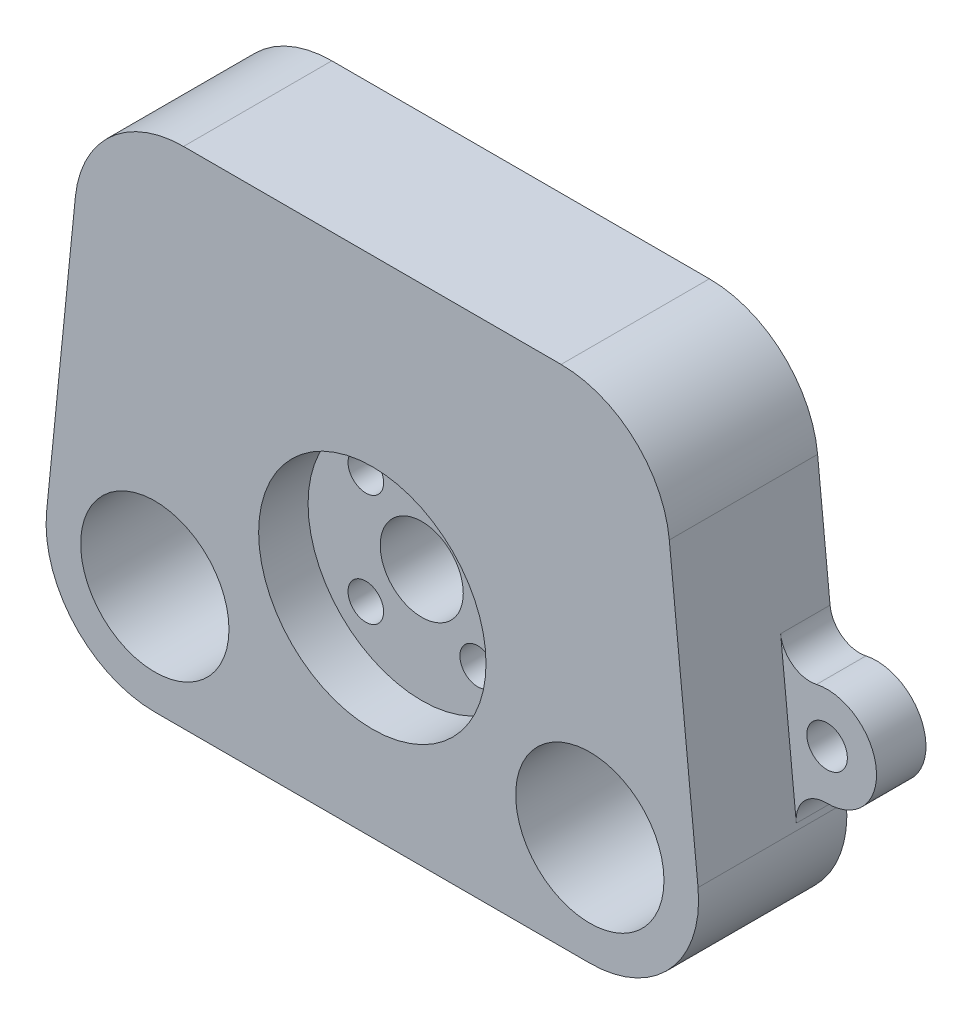
SolidWorks part; units mm, degrees
ref_plane "Front Plane" through (0, 0, 0) normal (0, 0, 1) x (1, 0, 0)
ref_plane "Top Plane" through (0, 0, 0) normal (0, 1, 0) x (1, 0, 0)
ref_plane "Right Plane" through (0, 0, 0) normal (1, 0, 0) x (0, 0, -1)
sketch "PosicionAgujeros" plane through (0, 0, 0) normal (0, 0, 1) x (1, 0, 0)
  line L0 (-18.25, 0) -> (18.25, 0) construction
  line L3 (22, -10) -> (-22, -10) construction
  line L7 (0, 0) -> (0, 20) construction
  line L8 (-20, 20) -> (20, 20) construction
  line L9 (0, 0) -> (5.6569, 5.6569) construction
  circle A1 centre (22, -10) radius 4 construction
  circle A2 centre (18.25, 0) radius 2.5 construction
  circle A3 centre (0, 0) radius 4 construction
  circle A4 centre (0, 0) radius 8 construction
  circle A6 centre (0, 0) radius 11 construction
  circle A7 centre (-20, 20) radius 10 construction
  circle A8 centre (20, 20) radius 10 construction
  point P2 (0, 0)
  point P8 (22, -10)
  point P9 (-18.25, 0)
  point P10 (18.25, 0)
  point P11 (0, -10)
  point P18 (-22, -10)
  point P24 (5.6569, 5.6569)
  point P26 (0, 20)
  dimension "D4" = 8
  dimension "D5" = 5
  dimension "D6" = 8
  dimension "D7" = 16
  dimension "D8" = 40
  dimension "D10" = 22
  dimension "D13" = 20
  dimension "D14" = 20
  dimension "D1" = 36.5
  dimension "D2" = 44
  dimension "D3" = 10
  dimension "D9" = 20
  dimension "D11" = 45
sketch "Croquis2" plane through (0, 0, 0) normal (0, 0, 1) x (1, 0, 0)
  line L0 (0, 0) -> (0, 20) construction
  line L1 (-34.1569, -21) -> (34.1569, -21)
  line L2 (-34.1569, -21) -> (-29.0484, 30)
  line L3 (-29.0484, 30) -> (29.0484, 30)
  line L4 (34.1569, -21) -> (29.0484, 30)
  line L5 (-34.1569, -21) -> (29.0484, 30) construction
  line L6 (-29.0484, 30) -> (34.1569, -21) construction
  circle A0 centre (22, -10) radius 7.5
  circle A2 centre (-22, -10) radius 7.5
  circle A4 centre (-20, 20) radius 10 construction
  circle A5 centre (-22, -10) radius 11 construction
  circle A6 centre (22, -10) radius 11 construction
  circle A9 centre (0, 0) radius 4.2
  point P3 (0, 6.561)
  dimension "D1" = 15
  dimension "D3" = 15
  dimension "D2" = 22
  dimension "D4" = 22
  dimension "D5" = 8.4
extrude "Saliente-Extruir1" add sketch "Croquis2" along normal blind 15
fillet "Redondeo2" radius 11 4 edges at (34.1569, -21, 7.5) (-34.1569, -21, 7.5) (29.0484, 30, 7.5) (-29.0484, 30, 7.5)
sketch "Croquis4" plane through (0, 0, 15) normal (0, 0, 1) x (1, 0, 0)
  circle A0 centre (0, 0) radius 11.5
  dimension "D1" = 23
extrude "Cortar-Extruir1" cut sketch "Croquis4" against normal blind 5
hole_wizard "Refrentado para tornillo con cabeza hueca de M31" positions "Croquis14" profile "Croquis16" counterbore size "M3" standard "DIN" end condition through all
sketch "Croquis14" plane through (0, 0, 0) normal (0, 0, -1) x (-1, 0, 0)
  point P0 (-5.6569, 5.6569)
sketch "Croquis16" plane through (5.6569, 5.6569, 0) normal (1, 0, 0) x (0, 1, 0)
  line L0 (0, 0) -> (0, 15)
  line L1 (0, 15) -> (1.8, 15)
  line L3 (1.8, 15) -> (1.8, 4.4)
  line L4 (1.8, 4.4) -> (3.25, 4.4)
  line L5 (3.25, 4.4) -> (3.25, 0)
  line L7 (3.25, 0) -> (0, 0)
  line L11 (0, -6.35) -> (0, 107.95) construction
  dimension "Diámetro de taladro hasta el siguiente" = 3.6
  dimension "Profundidad de taladro hasta el siguiente" = 15
  dimension "Diámetro de refrentado" = 6.5
  dimension "Profundidad de refrentado" = 4.4
pattern_circular "MatrizC1" count 4 over 360 about axis through (0, 0, 15) along (0, 0, -1) of "Refrentado para tornillo con cabeza hueca de M31"
sketch "Croquis17" plane through (0, 0, 0) normal (0, 0, 1) x (1, 0, 0)
  circle A8 centre (0, 20) radius 5
  point P1 (21.3832, -8.0688)
  point P8 (0, 20)
  dimension "D2" = 10
sketch "Croquis18" plane through (0, 0, 0) normal (0, 0, 1) x (1, 0, 0)
  circle A0 centre (36, 0) radius 2.05
  circle A1 centre (36, 0) radius 5
  point P3 (35, 0)
  dimension "D1" = 4.1
  dimension "D2" = 10
  dimension "D3" = 36
extrude "Saliente-Extruir2" add sketch "Croquis18" along normal blind 5
fillet "Redondeo3" radius 3 2 edges at (32.4011, -3.471, 2.5) (31.7841, 2.6882, 2.5)
equation "\"D3@Croquis2\"=\"D1@Croquis2\""
